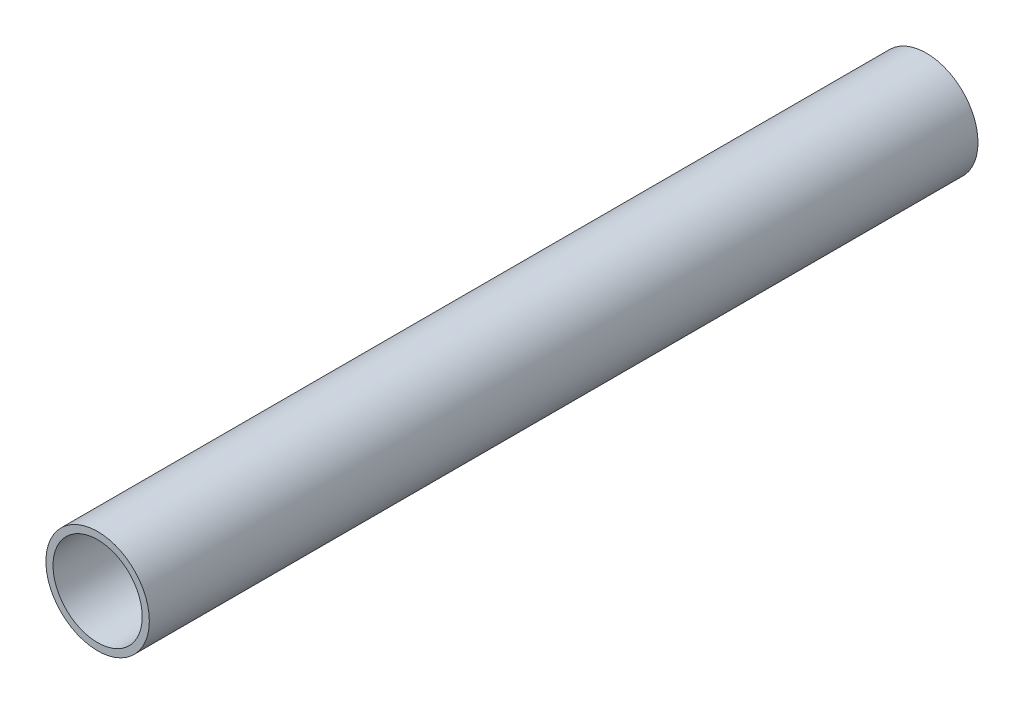
SolidWorks part; units mm, degrees
ref_plane "Front Plane" through (0, 0, 0) normal (0, 0, 1) x (1, 0, 0)
ref_plane "Top Plane" through (0, 0, 0) normal (0, 1, 0) x (1, 0, 0)
ref_plane "Right Plane" through (0, 0, 0) normal (1, 0, 0) x (0, 0, -1)
sketch "Sketch1" plane through (0, 0, 0) normal (0, 0, 1) x (1, 0, 0)
  circle A0 centre (0, 0) radius 8
  circle A1 centre (0, 0) radius 6.9
  dimension "D1" = 16
  dimension "D2" = 13.8
extrude "Boss-Extrude1" add sketch "Sketch1" along normal blind 128.2
sketch "Sketch2" plane through (0, 0, 0) normal (0, 1, 0) x (1, 0, 0)
  line L0 (-8, -128.2) -> (8, -128.2) construction
  circle A1 centre (0, -128.2) radius 2.5
extrude "Boss-Extrude2" [suppressed] add sketch "Sketch2" along normal blind 8 and the other way blind 8
